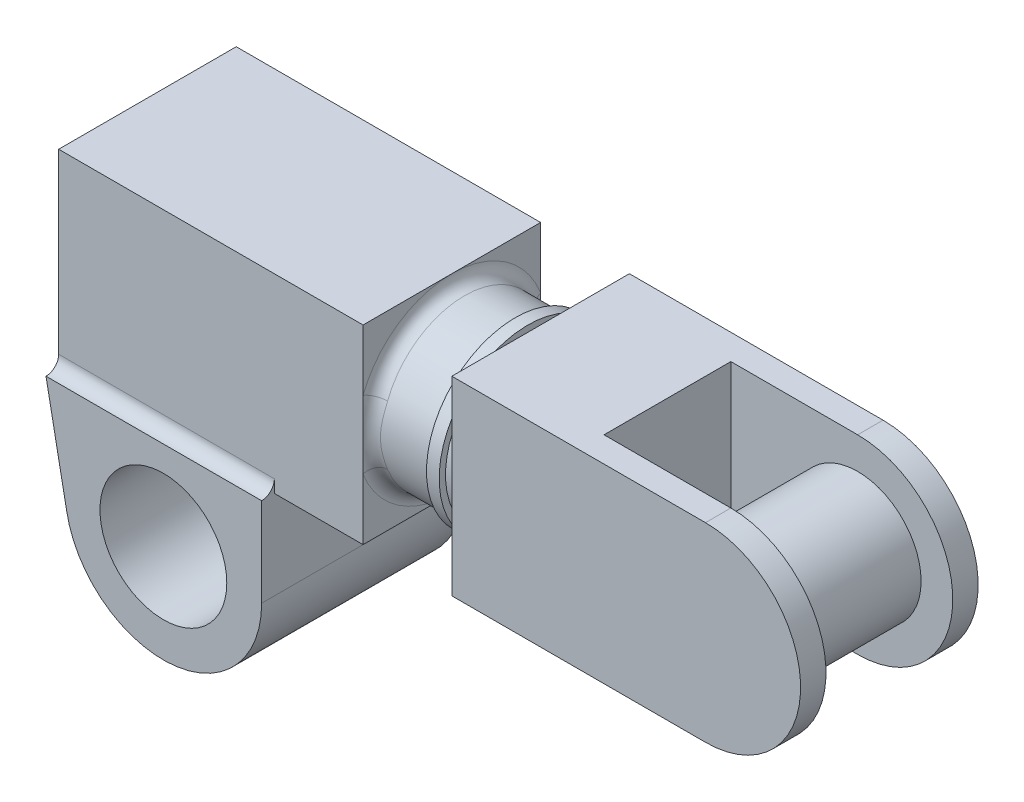
SolidWorks part; units mm, degrees
ref_plane "Front Plane" through (0, 0, 0) normal (0, 0, 1) x (1, 0, 0)
ref_plane "Top Plane" through (0, 0, 0) normal (0, 1, 0) x (1, 0, 0)
ref_plane "Right Plane" through (0, 0, 0) normal (1, 0, 0) x (0, 0, -1)
sketch "Sketch1" plane through (0, 0, 0) normal (1, 0, 0) x (0, 0, -1)
  line L1 (70, -75) -> (-70, -75)
  line L2 (70, -75) -> (70, 75)
  line L3 (70, 75) -> (-70, 75)
  line L4 (-70, -75) -> (-70, 75)
  line L5 (70, -75) -> (-70, 75) construction
  line L6 (70, 75) -> (-70, -75) construction
  point P0 (0, 0)
  dimension "D1" = 150
  dimension "D2" = 140
extrude "Boss-Extrude1" add sketch "Sketch1" along normal blind 240
sketch "Sketch2" plane through (240, 0, 0) normal (1, 0, 0) x (0, 0, -1)
  circle A0 centre (0, 0) radius 65
  dimension "D1" = 130
extrude "Boss-Extrude2" add sketch "Sketch2" along normal blind 50
sketch "Sketch3" plane through (290, 0, 0) normal (1, 0, 0) x (0, 0, -1)
  circle A0 centre (0, 0) radius 70
  dimension "D1" = 140
extrude "Boss-Extrude3" add sketch "Sketch3" along normal blind 10
sketch "Sketch4" plane through (0, 0, 0) normal (0, 0, 1) x (1, 0, 0)
  line L0 (0, -75) -> (16.2188, -158.4383)
  line L1 (0, 75) -> (0, -75) construction
  line L2 (170.0448, -145) -> (170.0448, -75)
  line L3 (240, -75) -> (0, -75) construction
  line L4 (0, -75) -> (170.0448, -75)
  arc A0 (16.2188, -158.4383) -> (170.0448, -145) centre (92.5448, -145) ccw
  circle A1 centre (92.5448, -145) radius 50
  dimension "D1" = 155
  dimension "D2" = 100
  dimension "D4" = 191
  dimension "D5" = 70
extrude "Boss-Extrude4" add sketch "Sketch4" along normal mid plane 160 contours A1 | L4 L2 A0 L0
fillet "Fillet1" radius 10 3 edges at (85.0224, -75, -70) (240, 0, -65) (85.0224, -75, 70)
sketch "Sketch5" plane through (300, 0, 0) normal (1, 0, 0) x (0, 0, -1)
  circle A0 centre (0, 0) radius 65
  dimension "D1" = 130
extrude "Boss-Extrude5" add sketch "Sketch5" along normal mid plane 20
sketch "Sketch6" plane through (0, 0, 0) normal (0, 0, 1) x (1, 0, 0)
  line L0 (510, 75) -> (310, 75)
  line L1 (310, 75) -> (310, -75)
  line L2 (310, -75) -> (510, -75)
  line L4 (310, -65) -> (310, 65) construction
  arc A0 (510, -75) -> (510, 75) centre (510, 0) ccw
  dimension "D1" = 150
  dimension "D2" = 200
extrude "Boss-Extrude7" add sketch "Sketch6" along normal mid plane 140
sketch "Sketch8" plane through (0, 0, 70) normal (0, 0, 1) x (1, 0, 0)
  arc A0 (510, -75) -> (510, 75) centre (510, 0) ccw construction
  arc A1 (510, -75) -> (510, 75) centre (510, 0) ccw
  arc A2 (510, -75) -> (510, 75) centre (510, 0) ccw
sketch "Sketch9" plane through (0, 0, 0) normal (0, 0, 1) x (1, 0, 0)
  line L0 (510, 75) -> (410, 75)
  line L1 (510, 75) -> (310, 75) construction
  line L2 (410, 75) -> (410, -75)
  line L3 (310, -75) -> (510, -75) construction
  line L4 (410, -75) -> (510, -75)
  arc A0 (510, -75) -> (510, 75) centre (510, 0) ccw construction
  arc A1 (510, -75) -> (510, 75) centre (510, 0) ccw
extrude "Cut-Extrude1" cut sketch "Sketch9" against normal mid plane 100
sketch "Sketch12" plane through (0, 0, -50) normal (0, 0, 1) x (1, 0, 0)
  circle A0 centre (510, 0) radius 50
extrude "Boss-Extrude8" add sketch "Sketch12" along normal up to next
